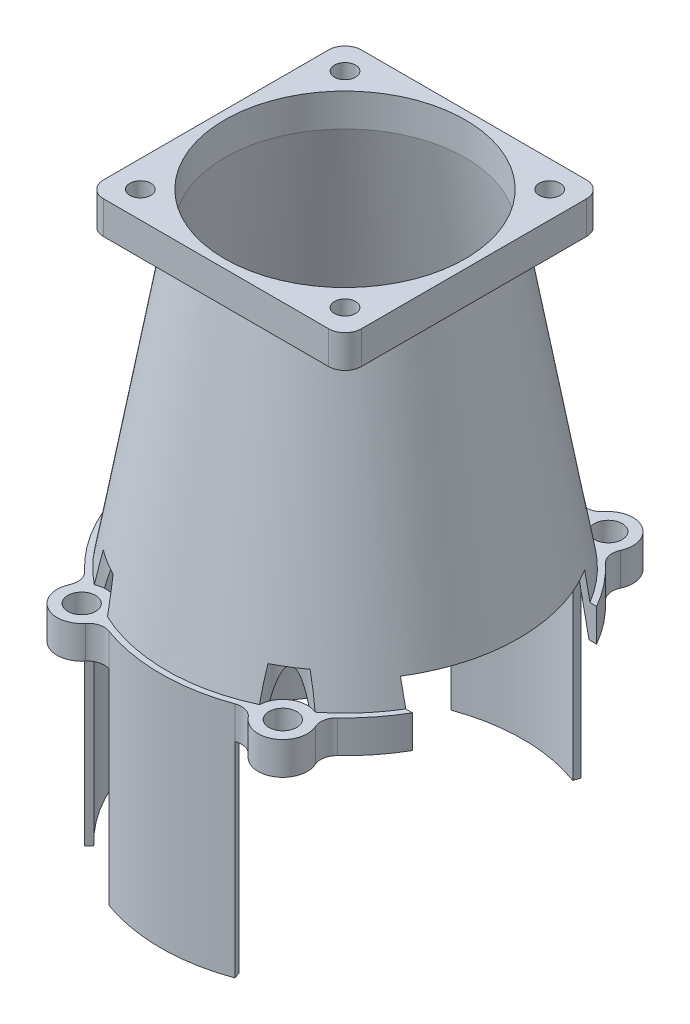
SolidWorks part; units mm, degrees
note: '?' marks a value the reader was unsure of. The reader was unsure of these and kept them because the rebuilt part matched: shared geometry of "Sketch1<139>", "Sketch2<111>", "Sketch7<3>".
ref_plane "Front Plane" through (0, 0, 0) normal (0, 0, 1) x (1, 0, 0)
ref_plane "Top Plane" through (0, 0, 0) normal (0, 1, 0) x (1, 0, 0)
ref_plane "Right Plane" through (0, 0, 0) normal (1, 0, 0) x (0, 0, -1)
sketch "Sketch1" plane through (0, 0, 0) normal (0, 1, 0) x (1, 0, 0)
  line L1 (20, -20) -> (-20, -20)
  line L2 (20, -20) -> (20, 20)
  line L3 (20, 20) -> (-20, 20)
  line L4 (-20, -20) -> (-20, 20)
  line L5 (20, -20) -> (-20, 20) construction
  line L6 (20, 20) -> (-20, -20) construction
  circle A0 centre (0, 0) radius 19.685
  circle A1 centre (0, 0) radius 18.669
  dimension "D3" = 39.37
  dimension "D1" = 40
  dimension "D2" = 40
  dimension "D4" = 1.016
ref_plane "Plane1" through (0, -50.8, 0) normal (0, 1, 0) x (1, 0, 0)
sketch "Sketch2" plane through (0, -50.8, 0) normal (0, 1, 0) x (1, 0, 0)
  circle A0 centre (0, 0) radius 28.575
  circle A1 centre (0, 0) radius 27.559
  dimension "D1" = 57.15
  dimension "D2" = 1.016
sketch "Sketch3" plane through (0, -50.8, 0) normal (0, 1, 0) x (1, 0, 0)
  line L1 (15.5956, -25.2476) -> (-15.5956, -25.2476)
  line L2 (15.5956, -25.2476) -> (15.5956, 25.2476)
  line L3 (15.5956, 25.2476) -> (-15.5956, 25.2476)
  line L4 (-15.5956, -25.2476) -> (-15.5956, 25.2476)
  line L5 (15.5956, -25.2476) -> (-15.5956, 25.2476) construction
  line L6 (15.5956, 25.2476) -> (-15.5956, -25.2476) construction
  circle A0 centre (15.5956, 25.2476) radius 3.81
  circle A1 centre (-15.5956, 25.2476) radius 3.81
  circle A2 centre (15.5956, -25.2476) radius 3.81
  circle A3 centre (-15.5956, -25.2476) radius 3.81
  point P0 (0, 0)
  dimension "D3" = 7.62
  dimension "D4" = 7.62
  dimension "D5" = 7.62
  dimension "D6" = 7.62
  dimension "D1" = 50.4952
  dimension "D2" = 31.1912
ref_axis "Axis1" through (0, -50.8, 0) along (0, 1, 0)?
loft "Loft1" add section "Sketch1" section "Sketch2"
loft "Cut-Loft1" cut section "Sketch1<139>" section "Sketch2<111>"
sketch "Sketch1<139>" plane through (0, 0, 0) normal (0, 1, 0) x (1, 0, 0) same geometry as "Sketch1"
sketch "Sketch2<111>" plane through (0, -50.8, 0) normal (0, 1, 0) x (1, 0, 0) same geometry as "Sketch2"
sketch "Sketch7" plane through (0, -50.8, 0) normal (0, -1, 0) x (1, 0, 0)
  circle A0 centre (0, 0) radius 27.559 construction
  circle A1 centre (0, 0) radius 27.559
  circle A2 centre (0, 0) radius 28.575 construction
  circle A3 centre (0, 0) radius 28.575
  circle A4 centre (15.5956, 25.2476) radius 3.81 construction
  circle A5 centre (15.5956, 25.2476) radius 3.81
  circle A6 centre (15.5956, -25.2476) radius 3.81 construction
  circle A7 centre (15.5956, -25.2476) radius 3.81
  circle A8 centre (-15.5956, -25.2476) radius 3.81 construction
  circle A9 centre (-15.5956, -25.2476) radius 3.81
  circle A10 centre (-15.5956, 25.2476) radius 3.81 construction
  circle A11 centre (-15.5956, 25.2476) radius 3.81
extrude "Boss-Extrude1" add sketch "Sketch7" against normal blind 5.08 contours A11 A3 A9 A1 | A11 A1 A5 A3 | A7 A3 A5 A1 | A9 A3 A7 A1
sketch "Sketch8" plane through (0, 0, 0) normal (0, 1, 0) x (1, 0, 0)
  line L0 (20, -20) -> (20, 20) construction
  line L1 (20, -20) -> (20, 20)
  line L2 (20, -20) -> (-20, -20) construction
  line L3 (20, -20) -> (-20, -20)
  line L4 (-20, -20) -> (-20, 20) construction
  line L5 (-20, -20) -> (-20, 20)
  line L6 (20, 20) -> (-20, 20) construction
  line L7 (20, 20) -> (-20, 20)
  circle A0 centre (0, 0) radius 18.669 construction
  circle A1 centre (0, 0) radius 18.669
extrude "Boss-Extrude2" add sketch "Sketch8" along normal blind 5.08
hole_wizard "#4 Clearance Hole1" positions "Sketch9" profile "Sketch10" hole size "#4" standard "ANSI Inch"
sketch "Sketch9" plane through (0, 5.08, 0) normal (0, 1, 0) x (1, 0, 0)
  line L0 (-20, 0) -> (20, 0) construction
  line L1 (-20, 20) -> (-20, -20) construction
  line L2 (20, -20) -> (20, 20) construction
  line L3 (0, 20) -> (0, -20) construction
  line L4 (20, 20) -> (-20, 20) construction
  point P0 (-15.875, 15.875)
  point P2 (15.875, 15.875)
  point P4 (15.875, -15.875)
  point P6 (-15.875, -15.875)
  dimension "D1" = 31.75
  dimension "D2" = 31.75
  dimension "D3" = 31.75
  dimension "D4" = 31.75
sketch "Sketch10" plane through (-15.875, 5.08, -15.875) normal (1, 0, 0) x (0, 0, 1)
  line L0 (0, 0) -> (0, 5.08)
  line L1 (0, 5.08) -> (1.6319, 5.08)
  line L2 (1.6319, 5.08) -> (1.6319, 0)
  line L5 (1.6319, 0) -> (0, 0)
  line L11 (0, -6.35) -> (0, 107.95) construction
  dimension "Thru Hole Dia." = 3.2639
  dimension "Thru Hole Depth" = 5.08
extrude "Cut-Extrude1" cut sketch "Sketch7<3>" against normal blind 5.08 from surface at -5.08 contours A11 | A5 | A7 | A9 starting at face at (0, -45.72, -27.686)
sketch "Sketch7<3>" plane through (0, -50.8, 0) normal (0, -1, 0) x (1, 0, 0) same geometry as "Sketch7"
hole_wizard "#8 Clearance Hole1" positions "Sketch12" profile "Sketch13" hole size "#8" standard "ANSI Inch" end condition up to next
sketch "Sketch12" plane through (0, -45.72, 0) normal (0, 1, 0) x (1, 0, 0)
  point P0 (-15.5956, -25.2476)
  point P3 (15.5956, -25.2476)
  point P6 (15.5956, 25.2476)
  point P9 (-15.5956, 25.2476)
sketch "Sketch13" plane through (-15.5956, -45.72, 25.2476) normal (1, 0, 0) x (0, 0, 1)
  line L0 (0, 0) -> (0, 5.08)
  line L1 (0, 5.08) -> (2.1526, 5.08)
  line L2 (2.1526, 5.08) -> (2.1526, 0)
  line L5 (2.1526, 0) -> (0, 0)
  line L11 (0, -6.35) -> (0, 107.95) construction
  dimension "Thru Hole Dia." = 4.3053
  dimension "Thru Hole Depth" = 5.08
fillet "Fillet2" radius 2.54 26 edges
fillet "Fillet3" radius 2.54 4 edges at (-20, 2.54, 20) (-20, 2.54, -20) (20, 2.54, -20) (20, 2.54, 20)
sketch "Sketch14" plane through (0, -50.8, 0) normal (0, -1, 0) x (1, 0, 0)
  line L0 (-19.6284, -20.7667) -> (-18.9305, -20.0284)
  line L1 (-19.6284, 20.7667) -> (-18.9305, 20.0284)
  line L2 (-9.7835, 26.848) -> (-9.4357, 25.8934)
  line L3 (9.7835, 26.848) -> (9.4357, 25.8934)
  line L4 (-9.4357, -25.8934) -> (-9.7835, -26.848)
  line L5 (9.4357, -25.8934) -> (9.7835, -26.848)
  arc A0 (-19.6284, 20.7667) -> (-19.6284, -20.7667) centre (0, 0) ccw construction
  arc A1 (-19.6284, 20.7667) -> (-19.6284, -20.7667) centre (0, 0) ccw
  arc A2 (-18.9305, 20.0284) -> (-18.9305, -20.0284) centre (0, 0) ccw
  arc A4 (9.7835, 26.848) -> (-9.7835, 26.848) centre (0, 0) ccw construction
  arc A5 (9.7835, 26.848) -> (-9.7835, 26.848) centre (0, 0) ccw
  arc A6 (-9.7835, -26.848) -> (9.7835, -26.848) centre (0, 0) ccw construction
  arc A7 (-9.7835, -26.848) -> (9.7835, -26.848) centre (0, 0) ccw
  arc A8 (9.4357, 25.8934) -> (-9.4357, 25.8934) centre (0, 0) ccw
  arc A9 (-9.4357, -25.8934) -> (9.4357, -25.8934) centre (0, 0) ccw
  dimension "D1" = 1.016
  dimension "D2" = 1.016
  dimension "D3" = 1.016
extrude "Boss-Extrude3" add sketch "Sketch14" along normal blind 31.75
sketch "Sketch15" plane through (0, -50.8, 0) normal (0, -1, 0) x (1, 0, 0)
  line L0 (-27.559, 0) -> (28.575, 0) construction
  line L2 (-9.4257, -14.2875) -> (43.8684, -14.2875)
  line L3 (-9.4257, -14.2875) -> (-9.4257, 14.2875)
  line L4 (-9.4257, 14.2875) -> (43.8684, 14.2875)
  line L5 (43.8684, -14.2875) -> (43.8684, 14.2875)
  line L6 (-9.4257, -14.2875) -> (43.8684, 14.2875) construction
  line L7 (-9.4257, 14.2875) -> (43.8684, -14.2875) construction
  arc A0 (-18.9305, 20.0284) -> (-18.9305, -20.0284) centre (0, 0) ccw construction
  arc A1 (19.6284, -20.7667) -> (19.6284, 20.7667) centre (0, 0) ccw construction
  point P8 (17.2213, 0)
  dimension "D1" = 28.575
extrude "Cut-Extrude2" cut sketch "Sketch15" against normal blind 9.0678
